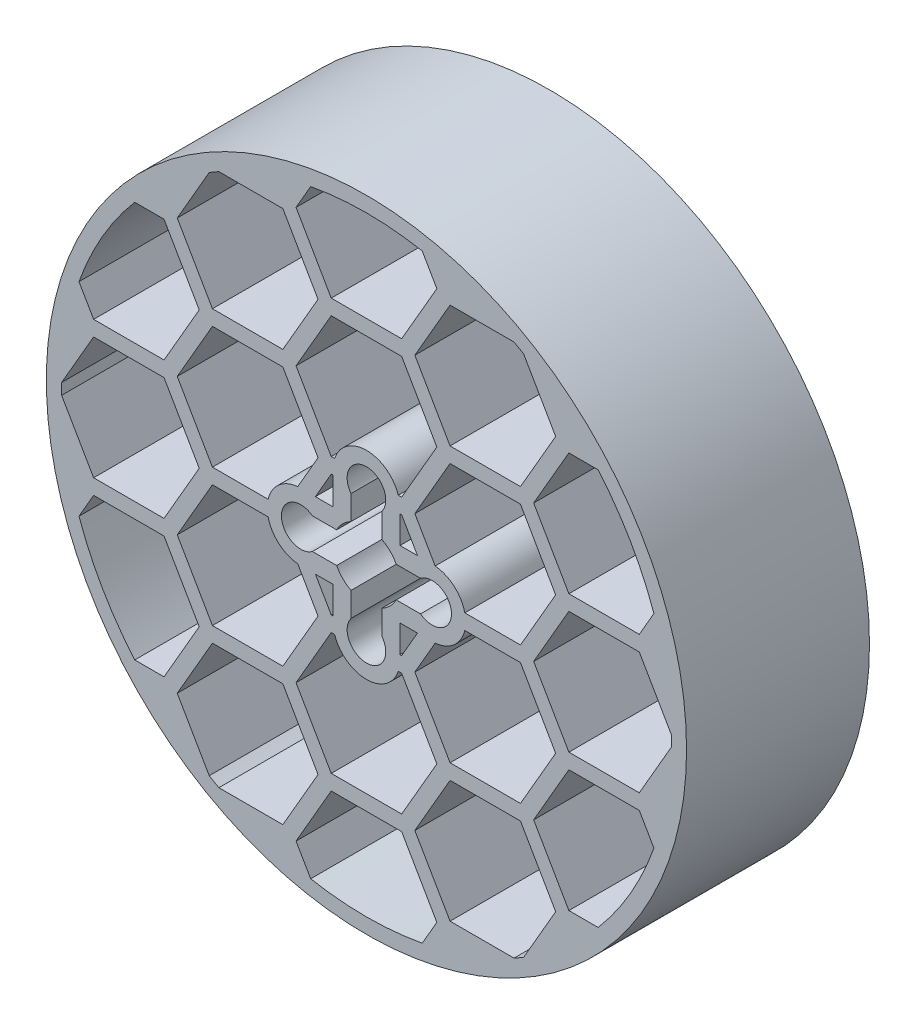
SolidWorks part; units mm, degrees
note: The reader was unsure of these and kept them because the rebuilt part matched: shared geometry of "Sketch1<4>".
ref_plane "Front Plane" through (0, 0, 0) normal (0, 0, 1) x (1, 0, 0)
ref_plane "Top Plane" through (0, 0, 0) normal (0, 1, 0) x (1, 0, 0)
ref_plane "Right Plane" through (0, 0, 0) normal (1, 0, 0) x (0, 0, -1)
sketch "Sketch1" plane through (0, 0, 0) normal (0, 0, 1) x (1, 0, 0)
  line L0 (-23.094, 45) -> (-11.547, 25)
  line L2 (-11.547, -20) -> (-11, -20)
  line L3 (11.547, -20) -> (16.7432, -11)
  line L4 (17.3205, 10) -> (17.2484, 10.1249)
  line L5 (11.547, 20) -> (11, 20)
  line L6 (-11.547, 20) -> (-16.7432, 11)
  line L7 (-11.547, 25) -> (-10.4443, 25)
  line L8 (11.547, 25) -> (23.094, 45)
  line L9 (23.094, 45) -> (11.547, 65)
  line L10 (11.547, 65) -> (-11.547, 65)
  line L11 (-11.547, 65) -> (-23.094, 45)
  line L12 (-23.094, 90) -> (-11.547, 70)
  line L13 (-11.547, 70) -> (11.547, 70)
  line L14 (11.547, 70) -> (23.094, 90)
  line L15 (23.094, 90) -> (18.2949, 98.3122)
  line L17 (-18.2949, 98.3122) -> (-23.094, 90)
  line L18 (-23.094, -45) -> (-11.547, -65)
  line L19 (-11.547, -65) -> (11.547, -65)
  line L20 (11.547, -65) -> (23.094, -45)
  line L21 (23.094, -45) -> (11.547, -25)
  line L22 (11.547, -25) -> (10.4443, -25)
  line L23 (-11.547, -25) -> (-23.094, -45)
  line L24 (-23.094, -90) -> (-18.2949, -98.3122)
  line L26 (18.2949, -98.3122) -> (23.094, -90)
  line L27 (23.094, -90) -> (11.547, -70)
  line L28 (11.547, -70) -> (-11.547, -70)
  line L29 (-11.547, -70) -> (-23.094, -90)
  line L30 (15.8771, 22.5) -> (22.5427, 10.9549)
  line L31 (32.2601, 2.5) -> (50.5181, 2.5)
  line L32 (50.5181, 2.5) -> (62.0652, 22.5)
  line L33 (62.0652, 22.5) -> (50.5181, 42.5)
  line L34 (50.5181, 42.5) -> (27.4241, 42.5)
  line L35 (27.4241, 42.5) -> (15.8771, 22.5)
  line L36 (22.5427, -10.9549) -> (15.8771, -22.5)
  line L37 (15.8771, -22.5) -> (27.4241, -42.5)
  line L38 (27.4241, -42.5) -> (50.5181, -42.5)
  line L39 (50.5181, -42.5) -> (62.0652, -22.5)
  line L40 (62.0652, -22.5) -> (50.5181, -2.5)
  line L41 (50.5181, -2.5) -> (32.2601, -2.5)
  line L42 (11.547, -25) -> (10.4443, -25)
  line L43 (-11.547, -25) -> (-23.094, -45)
  line L44 (-23.094, -45) -> (-11.547, -65)
  line L45 (-11.547, -65) -> (11.547, -65)
  line L46 (11.547, -65) -> (23.094, -45)
  line L47 (23.094, -45) -> (11.547, -25)
  line L48 (-15.8771, -22.5) -> (-22.5427, -10.9549)
  line L49 (-32.2601, -2.5) -> (-50.5181, -2.5)
  line L50 (-50.5181, -2.5) -> (-62.0652, -22.5)
  line L51 (-62.0652, -22.5) -> (-50.5181, -42.5)
  line L52 (-50.5181, -42.5) -> (-27.4241, -42.5)
  line L53 (-27.4241, -42.5) -> (-15.8771, -22.5)
  line L54 (-22.5427, 10.9549) -> (-15.8771, 22.5)
  line L55 (-15.8771, 22.5) -> (-27.4241, 42.5)
  line L56 (-27.4241, 42.5) -> (-50.5181, 42.5)
  line L57 (-50.5181, 42.5) -> (-62.0652, 22.5)
  line L58 (-62.0652, 22.5) -> (-50.5181, 2.5)
  line L59 (-50.5181, 2.5) -> (-32.2601, 2.5)
  line L60 (-11.547, 25) -> (-10.4443, 25)
  line L61 (11.547, 25) -> (23.094, 45)
  line L62 (23.094, 45) -> (11.547, 65)
  line L63 (11.547, 65) -> (-11.547, 65)
  line L64 (-11.547, 65) -> (-23.094, 45)
  line L65 (-23.094, 45) -> (-11.547, 25)
  line L66 (-27.4241, 47.5) -> (-15.8771, 67.5)
  line L67 (-15.8771, 67.5) -> (-27.4241, 87.5)
  line L68 (-27.4241, 87.5) -> (-48.4123, 87.5)
  line L69 (-51.5711, 85.6763) -> (-62.0652, 67.5)
  line L70 (-62.0652, 67.5) -> (-50.5181, 47.5)
  line L71 (-50.5181, 47.5) -> (-27.4241, 47.5)
  line L72 (-15.8771, -67.5) -> (-27.4241, -47.5)
  line L73 (-27.4241, -47.5) -> (-50.5181, -47.5)
  line L74 (-50.5181, -47.5) -> (-62.0652, -67.5)
  line L75 (-62.0652, -67.5) -> (-51.5711, -85.6763)
  line L76 (-48.4123, -87.5) -> (-27.4241, -87.5)
  line L77 (-27.4241, -87.5) -> (-15.8771, -67.5)
  line L78 (-66.3953, 25) -> (-54.8483, 45)
  line L79 (-54.8483, 45) -> (-66.3953, 65)
  line L80 (-66.3953, 65) -> (-75.9934, 65)
  line L82 (-94.2884, 33.3122) -> (-89.4893, 25)
  line L83 (-89.4893, 25) -> (-66.3953, 25)
  line L84 (-66.3953, -20) -> (-54.8483, 0)
  line L85 (-54.8483, 0) -> (-66.3953, 20)
  line L86 (-66.3953, 20) -> (-89.4893, 20)
  line L87 (-89.4893, 20) -> (-99.9834, 1.8237)
  line L88 (-99.9834, -1.8237) -> (-89.4893, -20)
  line L89 (-89.4893, -20) -> (-66.3953, -20)
  line L90 (-66.3953, -65) -> (-54.8483, -45)
  line L91 (-54.8483, -45) -> (-66.3953, -25)
  line L92 (-66.3953, -25) -> (-89.4893, -25)
  line L93 (-89.4893, -25) -> (-94.2884, -33.3122)
  line L95 (-75.9934, -65) -> (-66.3953, -65)
  line L96 (15.8771, 67.5) -> (27.4241, 47.5)
  line L97 (27.4241, 47.5) -> (50.5181, 47.5)
  line L98 (50.5181, 47.5) -> (62.0652, 67.5)
  line L99 (62.0652, 67.5) -> (51.5711, 85.6763)
  line L100 (48.4123, 87.5) -> (27.4241, 87.5)
  line L101 (27.4241, 87.5) -> (15.8771, 67.5)
  line L102 (27.4241, -47.5) -> (15.8771, -67.5)
  line L103 (15.8771, -67.5) -> (27.4241, -87.5)
  line L104 (27.4241, -87.5) -> (48.4123, -87.5)
  line L105 (51.5711, -85.6763) -> (62.0652, -67.5)
  line L106 (62.0652, -67.5) -> (50.5181, -47.5)
  line L107 (50.5181, -47.5) -> (27.4241, -47.5)
  line L108 (66.3953, -25) -> (54.8483, -45)
  line L109 (54.8483, -45) -> (66.3953, -65)
  line L110 (66.3953, -65) -> (75.9934, -65)
  line L112 (94.2884, -33.3122) -> (89.4893, -25)
  line L113 (89.4893, -25) -> (66.3953, -25)
  line L114 (66.3953, 20) -> (54.8483, 0)
  line L115 (54.8483, 0) -> (66.3953, -20)
  line L116 (66.3953, -20) -> (89.4893, -20)
  line L117 (89.4893, -20) -> (99.9834, -1.8237)
  line L118 (99.9834, 1.8237) -> (89.4893, 20)
  line L119 (89.4893, 20) -> (66.3953, 20)
  line L120 (66.3953, 65) -> (54.8483, 45)
  line L121 (54.8483, 45) -> (66.3953, 25)
  line L122 (66.3953, 25) -> (89.4893, 25)
  line L123 (89.4893, 25) -> (94.2884, 33.3122)
  line L125 (75.9934, 65) -> (66.3953, 65)
  line L126 (-11.547, -110) -> (11.547, -110) [skipped]
  line L127 (89.4893, -65) -> (101.0363, -45) [skipped]
  line L128 (101.0363, 45) -> (89.4893, 65) [skipped]
  line L129 (11.547, 110) -> (-11.547, 110) [skipped]
  line L130 (-89.4893, 65) -> (-101.0363, 45) [skipped]
  line L131 (-101.0363, -45) -> (-89.4893, -65) [skipped]
  line L132 (11, -20) -> (11.547, -20)
  line L133 (-11, 20) -> (-11.547, 20)
  line L134 (-10.4443, -25) -> (-11.547, -25)
  line L135 (-10.4443, -25) -> (-11.547, -25)
  line L136 (10.4443, 25) -> (11.547, 25)
  line L137 (10.4443, 25) -> (11.547, 25)
  line L138 (-5.0583, 17.7275) -> (-5.0583, 9.768)
  line L139 (5.0583, 17.7275) -> (5.0583, 9.768)
  line L140 (17.7275, 5.0583) -> (9.768, 5.0583)
  line L141 (17.7275, -5.0583) -> (9.768, -5.0583)
  line L142 (5.0583, -17.7275) -> (5.0583, -9.768)
  line L143 (-5.0583, -17.7275) -> (-5.0583, -9.768)
  line L144 (-17.7275, -5.0583) -> (-9.768, -5.0583)
  line L145 (-17.7275, 5.0583) -> (-9.768, 5.0583)
  line L146 (-21.548, 11) -> (-11, 11)
  line L147 (-11, 21.548) -> (-11, 11)
  line L148 (16.7432, 11) -> (11.547, 20)
  line L149 (21.548, 11) -> (11, 11)
  line L150 (11, 21.548) -> (11, 11)
  line L151 (11, -21.548) -> (11, -11)
  line L152 (21.548, -11) -> (11, -11)
  line L153 (-21.548, -11) -> (-11, -11)
  line L154 (-11, -21.548) -> (-11, -11)
  line L155 (-16.7432, -11) -> (-11.547, -20)
  line L156 (-17.3205, -10) -> (-17.2484, -10.1249) [skipped]
  circle A0 centre (0, 0) radius 100
  arc A1 (9.768, 5.0583) -> (5.0583, 9.768) centre (0, 0) ccw
  circle A2 centre (0, 0) radius 105
  arc A3 (-9.768, -5.0583) -> (-5.0583, -9.768) centre (0, 0) ccw
  arc A5 (21.548, -11) -> (21.548, 11) centre (21.548, 0) ccw
  arc A6 (-11, -21.548) -> (11, -21.548) centre (0, -21.548) ccw
  arc A7 (-21.548, 11) -> (-21.548, -11) centre (-21.548, 0) ccw
  arc A8 (11, 21.548) -> (-11, 21.548) centre (0, 21.548) ccw
  arc A9 (-5.0583, 9.768) -> (-9.768, 5.0583) centre (0, 0) ccw
  arc A10 (5.0583, -9.768) -> (9.768, -5.0583) centre (0, 0) ccw
  arc A11 (17.2484, 10.1249) -> (17.2479, 10.1247) centre (21.548, 0) ccw
  arc A14 (17.3205, 10) -> (17.2479, 10.1247) centre (0, 0) ccw construction
  circle A15 centre (0, 21.548) radius 3.175
  circle A16 centre (21.548, 0) radius 3.175
  circle A17 centre (0, -21.548) radius 3.175
  circle A18 centre (-21.548, 0) radius 3.175
  circle A19 centre (0, 21.548) radius 6.339
  circle A20 centre (21.548, 0) radius 6.339
  circle A21 centre (0, -21.548) radius 6.339
  circle A22 centre (-21.548, 0) radius 6.339
  arc A25 (-18.426, 0.5775) -> (-18.426, -0.5775) centre (0, 0) ccw
  arc A26 (0.5775, 18.426) -> (-0.5775, 18.426) centre (0, 0) ccw
  point P72 (0, 0)
  point P162 (0, 0)
  point P195 (0, 0)
  point P203 (0, 0)
  point P221 (0, 0)
  point P237 (0, 0)
  dimension "D15" = 2
  dimension "D19" = 5
  dimension "D20" = 4
  dimension "D21" = 4
  dimension "D22" = 4
  dimension "D24" = 11
  dimension "D25" = 12.678
  dimension "D26" = 6.35
  dimension "D27" = 10.548
  dimension "D5" = 5
  dimension "D17" = 5
  dimension "D18" = 5
  dimension "D2" = 3
  dimension "D3" = 3
  dimension "D4" = 2
  dimension "D7" = 2
  dimension "D8" = 2
  dimension "D9" = 2
  dimension "D10" = 3
  dimension "D11" = 2
  dimension "D12" = 2
  dimension "D13" = 2
  dimension "D14" = 3
  dimension "D6" = 6
  dimension "D16" = 4
  dimension "D23" = 4
extrude "Boss-Extrude1" add sketch "Sketch1" along normal blind 60
extrude "Boss-Extrude2" add sketch "Sketch1<4>" along normal blind 10 contours A19 A15 | A20 A16 | A22 A18 | A21 A17
sketch "Sketch1<4>" plane through (0, 0, 0) normal (0, 0, 1) x (1, 0, 0) same geometry as "Sketch1"
